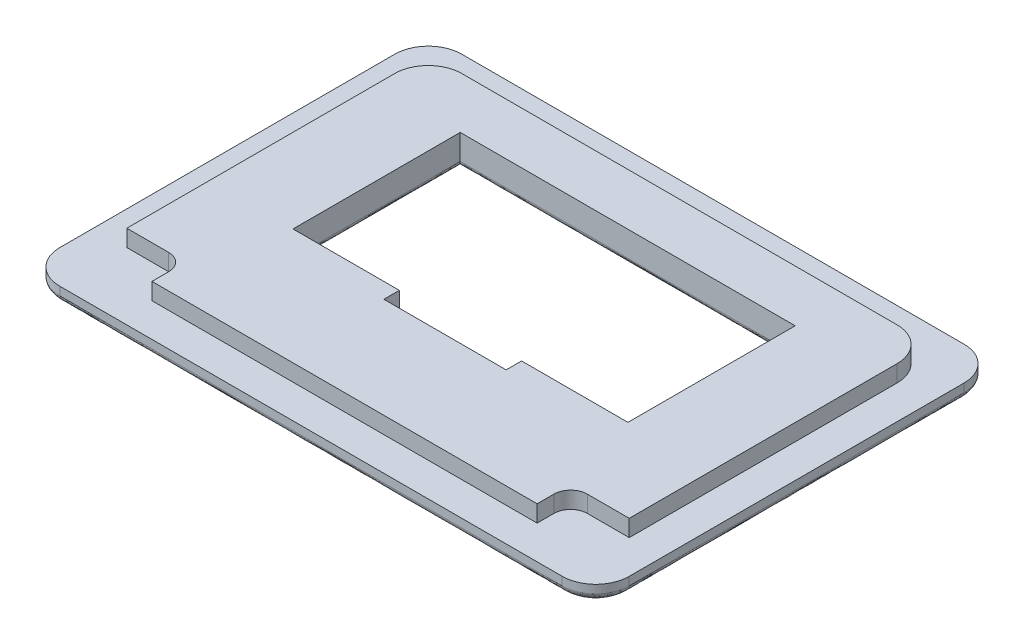
SolidWorks part; units mm, degrees
ref_plane "Front Plane" through (0, 0, 0) normal (0, 0, 1) x (1, 0, 0)
ref_plane "Top Plane" through (0, 0, 0) normal (0, 1, 0) x (1, 0, 0)
ref_plane "Right Plane" through (0, 0, 0) normal (1, 0, 0) x (0, 0, -1)
sketch "Sketch3" plane through (0, 0, 0) normal (0, 1, 0) x (1, 0, 0)
  line L0 (-11.5, -10) -> (11.5, -10)
  line L1 (-15, -8) -> (-15, 8)
  line L2 (-13, 10) -> (13, 10)
  line L3 (15, -8) -> (15, 8)
  line L4 (-15, 10) -> (15, -10) construction
  line L5 (-15, -12) -> (15, -12)
  line L6 (-17, -10) -> (-17, 10)
  line L7 (-15, 12) -> (15, 12)
  line L8 (17, -10) -> (17, 10)
  line L9 (-17, 12) -> (17, -12) construction
  line L10 (0, 12) -> (0, -10) construction
  line L15 (-15, 0) -> (15, 0) construction
  line L16 (-11.5, -9) -> (-11.5, -10)
  line L17 (-15, -8) -> (-12.5, -8)
  line L20 (11.5, -9) -> (11.5, -10)
  line L21 (15, -8) -> (12.5, -8)
  arc A2 (17, -10) -> (15, -12) centre (15, -10) cw
  arc A3 (-17, -10) -> (-15, -12) centre (-15, -10) ccw
  arc A4 (15, 12) -> (17, 10) centre (15, 10) cw
  arc A5 (-15, 12) -> (-17, 10) centre (-15, 10) ccw
  arc A6 (-13, 10) -> (-15, 8) centre (-13, 8) ccw
  arc A7 (13, 10) -> (15, 8) centre (13, 8) cw
  arc A9 (-12.5, -8) -> (-11.5, -9) centre (-12.5, -9) cw
  arc A10 (12.5, -8) -> (11.5, -9) centre (12.5, -9) ccw
  point P0 (0, 0)
  point P16 (0, 0)
  point P17 (-12, 9.5)
  dimension "D2" = 2
  dimension "D7" = 2
  dimension "D3" = 30
  dimension "D4" = 34
  dimension "D5" = 24
  dimension "D6" = 20
sketch "Sketch4" plane through (0, 0, 0) normal (0, 1, 0) x (1, 0, 0)
  line L0 (-11.5, -10) -> (11.5, -10)
  line L1 (-15, -8) -> (-15, 8)
  line L2 (-13, 10) -> (13, 10)
  line L3 (15, -8) -> (15, 8)
  line L4 (-11.5, -9) -> (-11.5, -10)
  line L5 (-15, -8) -> (-12.5, -8)
  line L6 (11.5, -9) -> (11.5, -10)
  line L7 (15, -8) -> (12.5, -8)
  arc A0 (-13, 10) -> (-15, 8) centre (-13, 8) ccw
  arc A1 (13, 10) -> (15, 8) centre (13, 8) cw
  arc A2 (-12.5, -8) -> (-11.5, -9) centre (-12.5, -9) cw
  arc A3 (12.5, -8) -> (11.5, -9) centre (12.5, -9) ccw
extrude "Boss-Extrude1" add sketch "Sketch4" along normal blind 2
extrude "Boss-Extrude2" add sketch "Sketch3" along normal blind 1 contours L8 A4 L7 A5 L6 A3 L5 A2
sketch "Sketch5" plane through (0, 2, 0) normal (0, 1, 0) x (1, 0, 0)
  line L0 (-13.4265, -4) -> (12.9043, -4) construction
  line L1 (-11.5, -10) -> (11.5, -10) construction
  line L2 (-15, -12) -> (15, -12) construction
  line L3 (-3.65, -4) -> (3.65, -4)
  line L4 (-10, 6.908) -> (10, 6.908)
  line L5 (-3.65, -4) -> (-3.65, -3.0769)
  line L6 (-10, 6.908) -> (-10, -3.0769)
  line L7 (-10, -3.0769) -> (-3.65, -3.0769)
  line L8 (0, 10) -> (0, -10) construction
  line L9 (-13, 10) -> (13, 10) construction
  line L10 (11.5, -10) -> (-11.5, -10) construction
  line L11 (10, -3.0769) -> (3.65, -3.0769)
  line L12 (10, 6.908) -> (10, -3.0769)
  line L13 (3.65, -4) -> (3.65, -3.0769)
  point P8 (0, -4)
  point P9 (0, -10)
  point P13 (0, 6.908)
  dimension "D1" = 6
  dimension "D2" = 7.3
  dimension "D3" = 20
extrude "Cut-Extrude1" cut sketch "Sketch5" against normal through all
sketch "Sketch7" plane through (0, 0, 0) normal (0, -1, 0) x (1, 0, 0)
  line L0 (-4.2193, 3.3748) -> (-3.9224, 3.3748)
  line L6 (0, 11.8852) -> (0, -9.5356) construction
  line L10 (3.9224, 4.3043) -> (3.9224, 3.3748)
  line L11 (4.2193, 0.8446) -> (4.2193, 3.3748)
  line L12 (4.2193, 3.3748) -> (3.9224, 3.3748)
  line L16 (-4.2193, 0.8446) -> (4.2193, 0.8446)
  line L17 (-3.9224, 4.3043) -> (3.9224, 4.3043)
  line L18 (-15, 12) -> (15, 12) construction
  line L19 (0, 12) -> (0, -12) construction
  line L20 (-15, -12) -> (15, -12) construction
  line L21 (-4.2193, 0.8446) -> (-4.2193, 3.3748)
  line L22 (-3.9224, 4.3043) -> (-3.9224, 3.3748)
  point P10 (0, 0.8446)
  point P12 (0, 4.3043)
extrude "Cut-Extrude2" cut sketch "Sketch7" against normal blind 1
fillet "Fillet2" radius 0.5 20 edges at (17, 0, 0) (16.4142, 0, -11.4142) (0, 0, -12) (-16.4142, 0, -11.4142) (-17, 0, 0) (-16.4142, 0, 11.4142) (0, 0, 12) (16.4142, 0, 11.4142) (4.2193, 0, 3.2259) (4.0708, 0, 3.3748) (3.9224, 0, 3.8396) (0, 0, 4.3043) (-3.9224, 0, 3.8396) (-4.0708, 0, 3.3748) (-4.2193, 0, 3.2259) (-10, 0, -1.9155) (0, 0, -6.908) (10, 0, -1.9155) (7.1096, 0, 3.0769) (-7.1096, 0, 3.0769) conic radius 1
